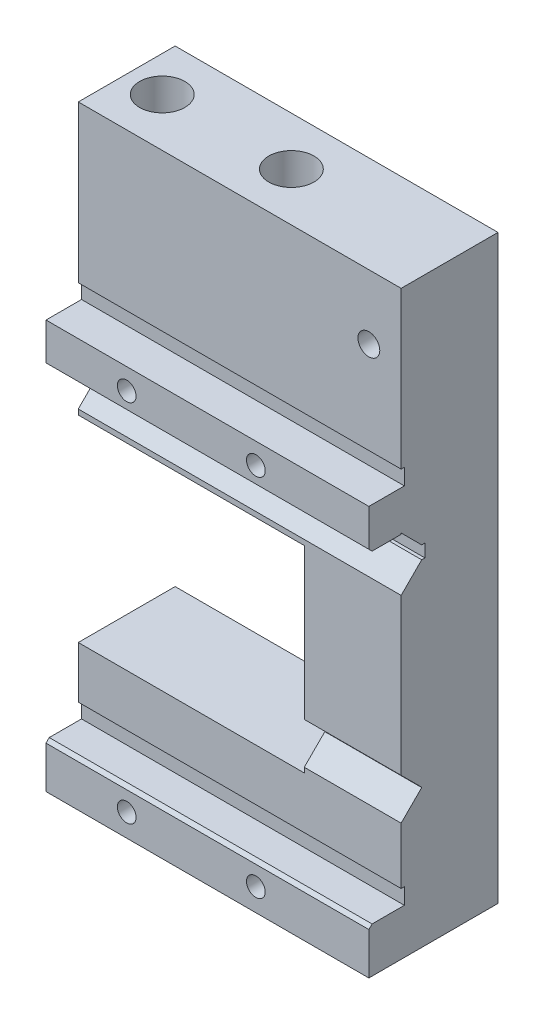
SolidWorks part; units mm, degrees
material "ABS"
ref_plane "Front Plane" through (0, 0, 0) normal (0, 0, 1) x (1, 0, 0)
ref_plane "Top Plane" through (0, 0, 0) normal (0, 1, 0) x (1, 0, 0)
ref_plane "Right Plane" through (0, 0, 0) normal (1, 0, 0) x (0, 0, -1)
sketch "Sketch1" plane through (0, 0, 0) normal (0, 0, 1) x (1, 0, 0)
  line L0 (-23.1034, -43.5723) -> (-23.1034, -8.5723)
  line L1 (-23.1034, 136.4277) -> (76.8966, 136.4277)
  line L2 (-23.1034, 136.4277) -> (-23.1034, 52.4277)
  line L3 (-23.1034, -43.5723) -> (76.8966, -43.5723)
  line L4 (76.8966, 136.4277) -> (76.8966, -43.5723)
  line L5 (-23.1034, 52.4277) -> (46.8966, 52.4277)
  line L7 (-23.1034, -8.5723) -> (46.8966, -8.5723)
  line L8 (46.8966, 52.4277) -> (46.8966, -8.5723)
  dimension "D1" = 61
  dimension "D2" = 180
  dimension "D3" = 84
  dimension "D4" = 100
  dimension "D6" = 70
extrude "Boss-Extrude1" add sketch "Sketch1" along normal blind 30
sketch "Sketch2" plane through (-23.1034, 0, 0) normal (-1, 0, 0) x (0, 0, 1)
  line L0 (30, 5.7917) -> (23.636, -0.5723)
  line L1 (30, 136.4277) -> (30, 52.4277) construction
  line L2 (23.636, -0.5723) -> (23.636, -0.6723)
  line L3 (23.636, -0.6723) -> (30, -7.0362)
  line L4 (30, -7.0362) -> (30, 5.7917)
  line L5 (30, -43.5723) -> (0, -43.5723) construction
  line L6 (30, 70.7917) -> (23.636, 64.4277)
  line L7 (30, -24.5723) -> (29, -24.5723)
  line L8 (30, -24.5723) -> (30, -29.5723)
  line L9 (30, -29.5723) -> (29, -29.5723)
  line L10 (29, -24.5723) -> (29, -29.5723)
  line L11 (23.636, 64.4277) -> (22.636, 64.4277)
  line L12 (22.636, 64.4277) -> (22.636, 60.4277)
  line L13 (22.636, 60.4277) -> (23.636, 60.4277)
  line L14 (23.636, 60.4277) -> (30, 54.0638)
  line L15 (30, 54.0638) -> (30, 70.7917)
  point P13 (29.5, -29.5723)
  dimension "D1" = 9
  dimension "D2" = 9
  dimension "D3" = 0.1
  dimension "D4" = 43
  dimension "D5" = 135
  dimension "D6" = 90
  dimension "D7" = 5
  dimension "D8" = 14
  dimension "D9" = 1
  dimension "D10" = 9
  dimension "D11" = 9
  dimension "D12" = 135
  dimension "D13" = 1
  dimension "D14" = 90
  dimension "D15" = 108
  dimension "D16" = 4
extrude "Cut-Extrude1" cut sketch "Sketch2" against normal blind 300
sketch "Sketch11" plane through (0, 0, 30) normal (0, 0, 1) x (1, 0, 0)
  line L0 (-23.1034, 136.4277) -> (-23.1034, 70.7917) construction
  line L1 (-23.1034, -29.5723) -> (76.8966, -29.5723)
  line L2 (-23.1034, -29.5723) -> (-23.1034, -43.5723)
  line L3 (-23.1034, -43.5723) -> (76.8966, -43.5723)
  line L4 (76.8966, -29.5723) -> (76.8966, -43.5723)
  line L5 (76.8966, 5.7917) -> (76.8966, 54.0638) construction
  line L6 (-23.1034, -43.5723) -> (76.8966, -43.5723) construction
  line L7 (76.8966, 82.9277) -> (-23.1034, 82.9277)
  line L8 (76.8966, 82.9277) -> (76.8966, 70.4277)
  line L9 (76.8966, 70.4277) -> (-23.1034, 70.4277)
  line L10 (-23.1034, 82.9277) -> (-23.1034, 70.4277)
  dimension "D1" = 14
  dimension "D2" = 12.5
  dimension "D3" = 100
extrude "Boss-Extrude2" add sketch "Sketch11" along normal blind 10
sketch "Sketch3" plane through (0, 136.4277, 0) normal (0, 1, 0) x (1, 0, 0)
  line L0 (-23.1034, -30) -> (-23.1034, 0) construction
  line L2 (76.8966, -30) -> (-23.1034, -30) construction
  circle A0 centre (-12.1034, -15) radius 3
  dimension "D1" = 11
  dimension "D2" = 15
extrude "Cut-Extrude2" cut sketch "Sketch3" against normal blind 100
sketch "Sketch4" plane through (0, 136.4277, 0) normal (0, 1, 0) x (1, 0, 0)
  circle A0 centre (-12.1034, -15) radius 7
  circle A1 centre (-12.1034, -15) radius 3 construction
extrude "Cut-Extrude3" cut sketch "Sketch4" against normal blind 70
pattern_linear "LPattern1" count 2 spacing 40 along (1, 0, 0) of "Cut-Extrude2", "Cut-Extrude3"
sketch "Sketch9" plane through (0, 0, 0) normal (0, 0, -1) x (-1, 0, 0)
  line L0 (-76.8966, -43.5723) -> (-76.8966, 136.4277) construction
  line L1 (-76.8966, 136.4277) -> (23.1034, 136.4277) construction
  circle A0 centre (-66.8966, 116.4277) radius 3.3818
  dimension "D1" = 10
  dimension "D2" = 20
extrude "Cut-Extrude8" cut sketch "Sketch9" against normal blind 100
sketch "Sketch10" plane through (0, 0, 30) normal (0, 0, 1) x (1, 0, 0)
  circle A0 centre (66.8966, 116.4277) radius 6.9825
  circle A1 centre (66.8966, 116.4277) radius 3.3818 construction
extrude "Cut-Extrude9" cut sketch "Sketch10" against normal blind 20 from offset 10 offset against normal yes
pattern_linear "LPattern4" count 2 spacing 140 along (-1, 0, 0) of "Cut-Extrude9", "Cut-Extrude8"
sketch "Sketch7" plane through (0, 0, 0) normal (0, 0, -1) x (-1, 0, 0)
  line L0 (23.1034, -43.5723) -> (-76.8966, -43.5723) construction
  line L1 (23.1034, 136.4277) -> (23.1034, 52.4277) construction
  circle A0 centre (-1.8966, -36.5723) radius 2.9002
  dimension "D1" = 7
  dimension "D2" = 25
extrude "Cut-Extrude6" cut sketch "Sketch7" against normal blind 40
sketch "Sketch8" plane through (0, 0, 0) normal (0, 0, -1) x (-1, 0, 0)
  circle A0 centre (-1.8966, -36.5723) radius 5.871
extrude "Cut-Extrude7" cut sketch "Sketch8" against normal blind 25
pattern_linear "Линейный массив1" count 2 spacing 40 along (1, 0, 0) count 2 spacing 113 along (0, 1, 0) of "Cut-Extrude6", "Cut-Extrude7"
sketch "Эскиз1" plane through (-23.1034, 0, 0) normal (-1, 0, 0) x (0, 0, 1)
  line L1 (30, 82.9277) -> (29, 82.9277)
  line L2 (30, 82.9277) -> (30, 87.9277)
  line L3 (30, 87.9277) -> (29, 87.9277)
  line L4 (29, 82.9277) -> (29, 87.9277)
  dimension "D1" = 5
  dimension "D2" = 1
extrude "Вырез-Вытянуть1" cut sketch "Эскиз1" against normal blind 200
chamfer "Фаска1" distance 1 angle 45 2 edges at (26.8966, 70.4277, 40) (26.8966, -29.5723, 40)
sketch "Эскиз3" plane through (0, -43.5723, 0) normal (0, -1, 0) x (1, 0, 0)
  line L0 (-23.1034, 0) -> (76.8966, 0) construction
  circle A0 centre (-59.8007, -15) radius 40
  dimension "D3" = 80
  dimension "D1" = 15
extrude "Вырез-Вытянуть3" cut sketch "Эскиз3" against normal blind 30
fillet "Скругление1" radius 3 1 edges at (-22.7198, -28.5723, 0)
